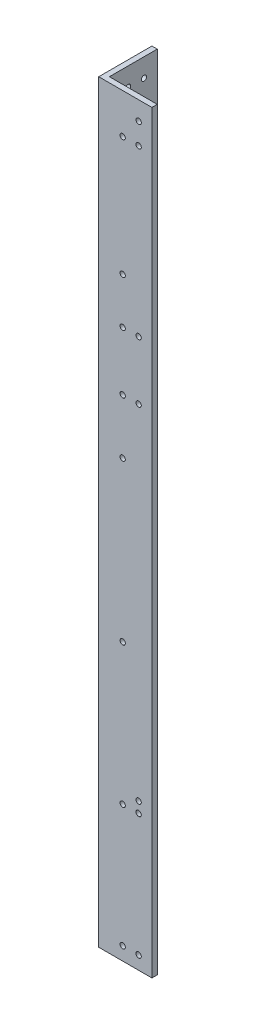
SolidWorks part; units mm, degrees
ref_plane "Front Plane" through (0, 0, 0) normal (0, 0, 1) x (1, 0, 0)
ref_plane "Top Plane" through (0, 0, 0) normal (0, 1, 0) x (1, 0, 0)
ref_plane "Right Plane" through (0, 0, 0) normal (1, 0, 0) x (0, 0, -1)
sketch "Sketch2" plane through (0, 0, 0) normal (0, 1, 0) x (1, 0, 0)
  line L0 (0, 31.75) -> (3.175, 31.75)
  line L1 (3.175, 31.75) -> (3.175, 3.175)
  line L2 (3.175, 3.175) -> (31.75, 3.175)
  line L3 (31.75, 3.175) -> (31.75, 0)
  line L4 (31.75, 0) -> (0, 0)
  line L5 (0, 0) -> (0, 31.75)
  point P9 (1.5875, 31.75)
  point P10 (31.75, 1.5875)
  dimension "D4" = 3.175
  dimension "D1" = 31.75
  dimension "D2" = 31.75
  dimension "D3" = 3.175
extrude "Boss-Extrude1" add sketch "Sketch2" along normal blind 450
sketch "RightSideHoles-Sketch3" plane through (0, 0, 0) normal (0, 0, 1) x (1, 0, 0)
  line L0 (0, 0) -> (31.75, 0) construction
  line L1 (0, 450) -> (31.75, 450) construction
  line L3 (0, 450) -> (0, 0) construction
  circle A0 centre (14.2875, 81.1125) radius 1.5875
  circle A1 centre (23.8125, 81.1125) radius 1.5875
  circle A3 centre (23.8125, 87.4625) radius 1.5875
  circle A5 centre (14.2875, 426.1875) radius 1.5875
  circle A6 centre (23.8125, 438.8875) radius 1.5875
  circle A7 centre (23.8125, 426.1875) radius 1.5875
  circle A8 centre (14.2875, 327.6026) radius 1.5875
  circle A9 centre (23.8125, 327.6026) radius 1.5875
  circle A10 centre (14.2875, 292.6776) radius 1.5875
  circle A11 centre (23.8125, 292.6776) radius 1.5875
  circle A12 centre (14.2875, 7.9375) radius 1.5875
  circle A13 centre (23.8125, 7.9375) radius 1.5875
  circle A14 centre (14.2875, 165) radius 1.5875
  circle A15 centre (14.2875, 260) radius 1.5875
  circle A16 centre (14.2875, 355) radius 1.5875
  dimension "D4" = 3.175
  dimension "D1" = 81.1125
  dimension "D2" = 14.2875
  dimension "D12" = 7.9375
  dimension "D7" = 34.925
  dimension "D3" = 9.525
  dimension "D10" = 327.6026
  dimension "D11" = 165
  dimension "D13" = 95
  dimension "D14" = 95
  dimension "D5" = 6.35
  dimension "D6" = 12.7
  dimension "D8" = 11.1125
sketch "FrontSideHoles-Sketch4" plane through (0, 0, 0) normal (-1, 0, 0) x (0, 0, 1)
  line L0 (-31.75, 450) -> (0, 450) construction
  line L1 (0, 450) -> (0, 0) construction
  line L3 (-31.75, 0) -> (0, 0) construction
  circle A0 centre (-23.8125, 81.1125) radius 1.5875
  circle A2 centre (-23.8125, 87.4625) radius 1.5875
  circle A3 centre (-14.2875, 87.4625) radius 1.5875
  circle A4 centre (-23.8125, 438.8875) radius 1.5875
  circle A5 centre (-14.2875, 438.8875) radius 1.5875
  circle A6 centre (-23.8125, 426.1875) radius 1.5875
  circle A8 centre (-14.2875, 333.1776) radius 2
  circle A9 centre (-14.2875, 314.6526) radius 2
  circle A10 centre (-14.2875, 165) radius 1.5875
  circle A11 centre (-14.2875, 260) radius 1.5875
  circle A12 centre (-14.2875, 355) radius 1.5875
  circle A13 centre (-23.8125, 7.9375) radius 1.5875
  circle A14 centre (-14.2875, 7.9375) radius 1.5875
  dimension "D4" = 3.175
  dimension "D13" = 95
  dimension "D14" = 95
  dimension "D5" = 6.35
  dimension "D16" = 4
  dimension "D6" = 11.1125
  dimension "D9" = 18.525
  dimension "D10" = 14.2875
  dimension "D7" = 12.7
  dimension "D8" = 314.6526
  dimension "D12" = 165
  dimension "D15" = 7.9375
  dimension "D2" = 14.2875
  dimension "D11" = 9.525
  dimension "D3" = 81.1125
extrude "RightSideHoles-Cut-Extrude1" cut sketch "RightSideHoles-Sketch3" against normal blind 3.175
extrude "FrontSideHoles-Cut-Extrude2" cut sketch "FrontSideHoles-Sketch4" against normal blind 3.175
equation "\"RailThickness\"= .125in'Spec"
equation "\"VSWidth\"= 1.25in'Spec"
equation "\"VSHeight\"= 1.25in'Spec"
equation "\"VSLength\"= 450mm"
equation "\"HoleOffsetFromEdge\"= \"RailThickness\" * 2.5"
equation "\"HoleOffsetFromSide\"= \"RailThickness\" * 3.5"
equation "\"LegHeight\"= 70mm'Space needed for PSU/Stepper/Electronics"
equation "\"VSBottomSideRailHoleY1FromBottomOfLowerRail\"= \"V1 BottomOfLowerRail\" + \"HoleOffsetFromSide\"'Equals 70.1125"
equation "\"VSSideRailHoleX1FromSide\"= \"HoleOffsetFromSide\" + \"RailThickness\""
equation "\"FasteningHoleDiameter\"= .125in"
equation "\"VSBottomSideRailHoleY2FromY1\"= \"LowerRailHeight\" - \"HoleOffsetFromSide\" - \"HoleOffsetFromEdge\"'Equals 6.35"
equation "\"VSTopSideRailHoleY1FromEdge\"= \"HoleOffsetFromEdge\" + \"RailThickness\""
equation "\"D4@RightSideHoles-Sketch3\" = \"FasteningHoleDiameter\""
equation "\"D1@RightSideHoles-Sketch3\" = \"VSBottomSideRailHoleY1FromBottomOfLowerRail\""
equation "\"D2@RightSideHoles-Sketch3\" = \"VSSideRailHoleX1FromSide\""
equation "\"D1@Boss-Extrude1\"=\"VSLength\""
equation "\"D4@FrontSideHoles-Sketch4\" = \"FasteningHoleDiameter\""
equation "\"D6@FrontSideHoles-Sketch4\" = \"VSTopSideRailHoleY1FromEdge\""
equation "\"VSMidSideRailHoleY1FromV8TopOfMidSideRail\"= \"V8 ToTopOfMidSideRail\" - \"HoleOffsetFromEdge\"'Equals 308.2875"
equation "\"LowerRailHeight\"= 1.00in"
equation "\"D2@Sketch2\"=\"VSWidth\""
equation "\"D1@Sketch2\"=\"VSHeight\""
equation "\"TopRailHeight\"= 1.25in"
equation "\"MidLeftOrRightSideRailHeight\"= 2.0in"
equation "\"D12@RightSideHoles-Sketch3\"=\"HoleOffsetFromEdge\""
equation "\"VSMidSideRailHoleY2FromY1\"= \"MidLeftOrRightSideRailHeight\" - \"HoleOffsetFromEdge\" * 2'Equals 34.925"
equation "\"D7@RightSideHoles-Sketch3\"=\"VSMidSideRailHoleY2FromY1\""
equation "\"VSTopSideRailHoleY2FromY1\"= \"TopRailHeight\" - \"VSTopSideRailHoleY1FromEdge\" - \"HoleOffsetFromEdge\"'Equals 12.7"
equation "\"D7@FrontSideHoles-Sketch4\"=\"VSTopSideRailHoleY2FromY1\""
equation "\"VSSideRailHoleX2FromX1\"= \"VSWidth\" - \"VSSideRailHoleX1FromSide\" - \"HoleOffsetFromEdge\""
equation "\"D3@RightSideHoles-Sketch3\"=\"VSSideRailHoleX2FromX1\""
equation "\"1mmSpacer\"= 1mm"
equation "\"20TGT2PulleyWidth\"= 8.7mm'The STL of the Pulley in the diagram is a bit larger"
equation "\"BeltTensionerUpperLowerWallThickness\"= 7mm"
equation "\"BeltTensionerInnerHeight\"= \"20TGT2PulleyWidth\" * 2 + \"1mmSpacer\" * 3"
equation "\"BeltTensionerHeight\"= \"BeltTensionerInnerHeight\" + \"BeltTensionerUpperLowerWallThickness\" * 2"
equation "\"D9@FrontSideHoles-Sketch4\"=\"VSBeltTensionerHoleY2FromY1\""
equation "\"VSBeltTensionerHoleY1FromBottom\"= \"V9 FromBottomGantryPulleyToBottomOfBeltTensioner\" + \"HoleOffsetFromEdge\""
equation "\"VSBeltTensionerHoleY2FromY1\"= \"BeltTensionerHeight\" - \"HoleOffsetFromEdge\" * 2"
equation "\"V1 BottomOfLowerRail\"= \"LegHeight\""
equation "\"StepperShaftLength\"= 24mm'Pulley will be attached to the end"
equation "\"ZAxisLeadScrewLength\"= 200mm"
equation "\"LM8UUHeight\"= 24mm'Spec"
equation "\"V2 ToBedAtTopOfZAxis\"= \"V1 BottomOfLowerRail\" - \"LowerEnclosureThickness\" + \"StepperShaftLength\" + \"ZAxisLeadScrewLength\" - \"LM8UUHeight\" / 2"
equation "\"HotEndToTopOfXAxisGB\"= 63.315144mm'Measured from the100.Should be 63.315144"
equation "\"TopOfGBToBottomOfLinearRail\"= \"LinearGBWidth\" / 2 + \"LinearRailWidth\" / 2"
equation "\"LinearGBWidth\"= 27mm'Spec"
equation "\"V5 ToBottomOfXAxisLinearRail\"= \"V4 ToTopOfBuildPlate/HotEndTip\" + \"HotEndToTopOfXAxisGB\" - \"TopOfGBToBottomOfLinearRail\""
equation "\"LinearRailWidth\"= 12mm'Spec"
equation "\"V6 ToBottomOfGantryPulley\"= \"V5 ToBottomOfXAxisLinearRail\" - \"DistanceFromGABTopToLowerPulley\""
equation "\"GABUpperHeight\"= 6mm"
equation "\"GABMidWallHeight\"= 28mm'Must equal 28 or changes alignment"
equation "\"GABMidShortRiserHeight\"= \"GABMidWallHeight\" / 2 - \"20TGT2PulleyWidth\"'Equals 5.3"
equation "\"GABRiserBossOffset\"= 0.8mm'Aligns Pulleys"
equation "\"DistanceFromGABTopToLowerPulley\"= \"GABUpperHeight\" + \"GABMidWallHeight\" - \"GABMidShortRiserHeight\" + \"GABRiserBossOffset\" / 2"
equation "\"V7 ToTopOfMidBackRail\"= \"V6 ToBottomOfGantryPulley\" + \"StepperShaftLength\""
equation "\"D10@RightSideHoles-Sketch3\"=\"VSMidSideRailHoleY1FromV8TopOfMidSideRail\""
equation "\"BedToBuildPlateStandoffLength\"= 15mm"
equation "\"BuildPlateHeight\"= 8mm'Spec"
equation "\"V4 ToTopOfBuildPlate/HotEndTip\"= \"V2 ToBedAtTopOfZAxis\" + \"BedToBuildPlateStandoffLength\" + \"BuildPlateHeight\""
equation "\"D8@FrontSideHoles-Sketch4\"=\"VSBeltTensionerHoleY1FromBottom\""
equation "\"V8 ToTopOfMidSideRail\"= \"V7 ToTopOfMidBackRail\" - \"RailThickness\""
equation "\"V9 FromBottomGantryPulleyToBottomOfBeltTensioner\"= \"V6 ToBottomOfGantryPulley\" - \"BeltTensionerUpperLowerWallThickness\" - \"1mmSpacer\""
equation "\"BeltTensionerMountingHoleOffsetFromEdge\"= \"HoleOffsetFromEdge\""
equation "\"VSBeltTensionerXMountingHoleOffsetFromSide\"= \"BeltTensionerMountingHoleOffsetFromEdge\" + \"RailThickness\" * 2"
equation "\"D10@FrontSideHoles-Sketch4\"=\"VSBeltTensionerXMountingHoleOffsetFromSide\""
equation "\"VSEnclosureOffsets\"= ( \"VSLength\" - \"LegHeight\" ) / 4"
equation "\"D11@RightSideHoles-Sketch3\"=\"LegHeight\" + \"VSEnclosureOffsets\""
equation "\"D13@RightSideHoles-Sketch3\"=\"VSEnclosureOffsets\""
equation "\"D14@RightSideHoles-Sketch3\"=\"VSEnclosureOffsets\""
equation "\"D12@FrontSideHoles-Sketch4\"= \"LegHeight\" + \"VSEnclosureOffsets\""
equation "\"D13@FrontSideHoles-Sketch4\"=\"VSEnclosureOffsets\""
equation "\"D14@FrontSideHoles-Sketch4\"=\"VSEnclosureOffsets\""
equation "\"D15@FrontSideHoles-Sketch4\"=\"HoleOffsetFromEdge\""
equation "\"D2@FrontSideHoles-Sketch4\"=\"VSSideRailHoleX1FromSide\""
equation "\"D5@FrontSideHoles-Sketch4\"=\"VSBottomSideRailHoleY2FromY1\""
equation "\"D3@FrontSideHoles-Sketch4\"=\"VSBottomSideRailHoleY1FromBottomOfLowerRail\""
equation "\"D5@RightSideHoles-Sketch3\"=\"VSBottomSideRailHoleY2FromY1\""
equation "\"D6@RightSideHoles-Sketch3\"=\"VSTopSideRailHoleY2FromY1\""
equation "\"D8@RightSideHoles-Sketch3\"=\"VSTopSideRailHoleY1FromEdge\""
equation "\"BeltTensionerMountingHoleDiameter\"= 4.0mm"
equation "\"D16@FrontSideHoles-Sketch4\"=\"BeltTensionerMountingHoleDiameter\""
equation "\"LowerEnclosureThickness\"= 5mm"
